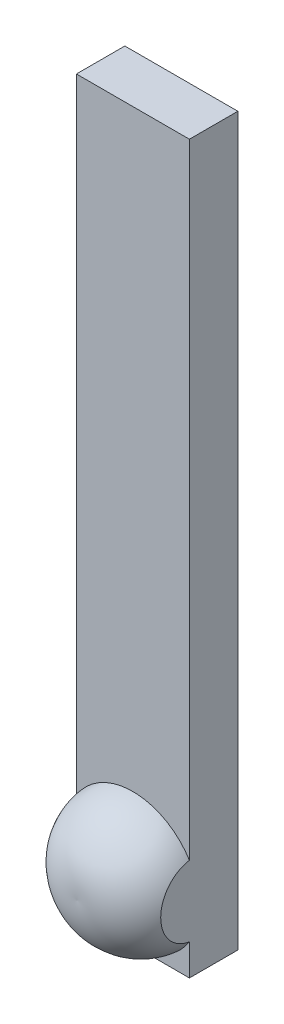
SolidWorks part; units mm, degrees
ref_plane "Front Plane" through (0, 0, 0) normal (1, 0, 0) x (0, 1, 0)
ref_plane "Top Plane" through (0, 0, 0) normal (0, 0, 1) x (0, 1, 0)
ref_plane "Right Plane" through (0, 0, 0) normal (0, 1, 0) x (-1, 0, 0)
sketch "Sketch1" plane through (0, 0, 0) normal (0, 0, 1) x (0, 1, 0)
  line L5 (0, 0) -> (57.15, 0)
  line L6 (0, 0) -> (0, 8.89)
  line L7 (0, 8.89) -> (57.15, 8.89)
  line L8 (57.15, 0) -> (57.15, 8.89)
  dimension "D1" = 8.89
  dimension "D2" = 57.15
extrude "Boss-Extrude1" add sketch "Sketch1" along normal blind 3.81
ref_plane "Plane1" through (-4.445, 0, 0) normal (1, 0, 0) x (0, 1, 0)
sketch "Sketch2" plane through (-4.445, 0, 0) normal (1, 0, 0) x (0, 1, 0)
  line L0 (5.2423, 8.1921) -> (5.2423, 3.81)
  line L1 (0, 3.81) -> (57.15, 3.81) construction
  line L2 (5.2423, 3.81) -> (0, 3.81)
  arc A0 (0, 3.81) -> (5.2423, 8.1921) centre (4.8122, 3.3799) cw
revolve "Revolve1" add sketch "Sketch2" angle 360 about L0
sketch "Sketch3" plane through (0, 0, 0) normal (0, -1, 0) x (1, 0, 0)
  line L1 (-8.89, 0) -> (-10.3809, 0)
  line L2 (-8.89, 0) -> (-8.89, 8.0093)
  line L3 (-8.89, 8.0093) -> (-10.3809, 8.0093)
  line L4 (-10.3809, 0) -> (-10.3809, 8.0093)
  line L5 (0, 0) -> (1.1414, 0)
  line L6 (0, 0) -> (0, 7.3991)
  line L7 (0, 7.3991) -> (1.1414, 7.3991)
  line L8 (1.1414, 0) -> (1.1414, 7.3991)
extrude "Cut-Extrude1" cut sketch "Sketch3" against normal through all
